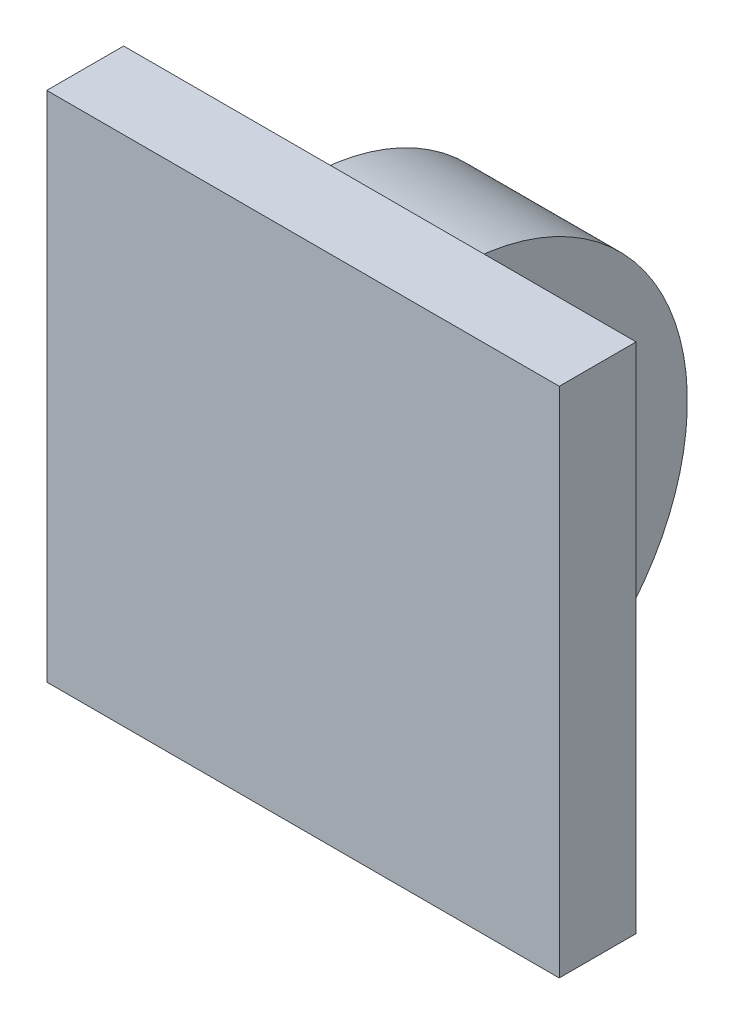
SolidWorks part; units mm, degrees
ref_plane "Alzado" through (0, 0, 0) normal (0, 0, 1) x (1, 0, 0)
ref_plane "Planta" through (0, 0, 0) normal (0, 1, 0) x (1, 0, 0)
ref_plane "Vista lateral" through (0, 0, 0) normal (1, 0, 0) x (0, 0, -1)
sketch "Croquis1" plane through (0, 0, 0) normal (0, 0, 1) x (1, 0, 0)
  line L1 (-5, 5) -> (5, 5)
  line L2 (-5, 5) -> (-5, -5)
  line L3 (-5, -5) -> (5, -5)
  line L4 (5, 5) -> (5, -5)
  line L5 (-5, 5) -> (5, -5) construction
  line L6 (-5, -5) -> (5, 5) construction
  point P0 (0, 0)
  dimension "D1" = 10
  dimension "D2" = 10
extrude "Saliente-Extruir6" add sketch "Croquis1" along normal blind 1.5
sketch "Croquis8" plane through (0, 0, 0) normal (1, 0, 0) x (0, 0, -1)
  line L0 (0, -5) -> (0, 5) construction
  line L1 (0, 4.5) -> (0, 2.5)
  line L2 (0, -2.5) -> (0, -4.5)
  arc A0 (0, -2.5) -> (0, 2.5) centre (0, 0) ccw
  arc A1 (0, -4.5) -> (0, 4.5) centre (0, 0) ccw
  dimension "D1" = 5
  dimension "D2" = 2
extrude "Saliente-Extruir7" add sketch "Croquis8" along normal mid plane 3
